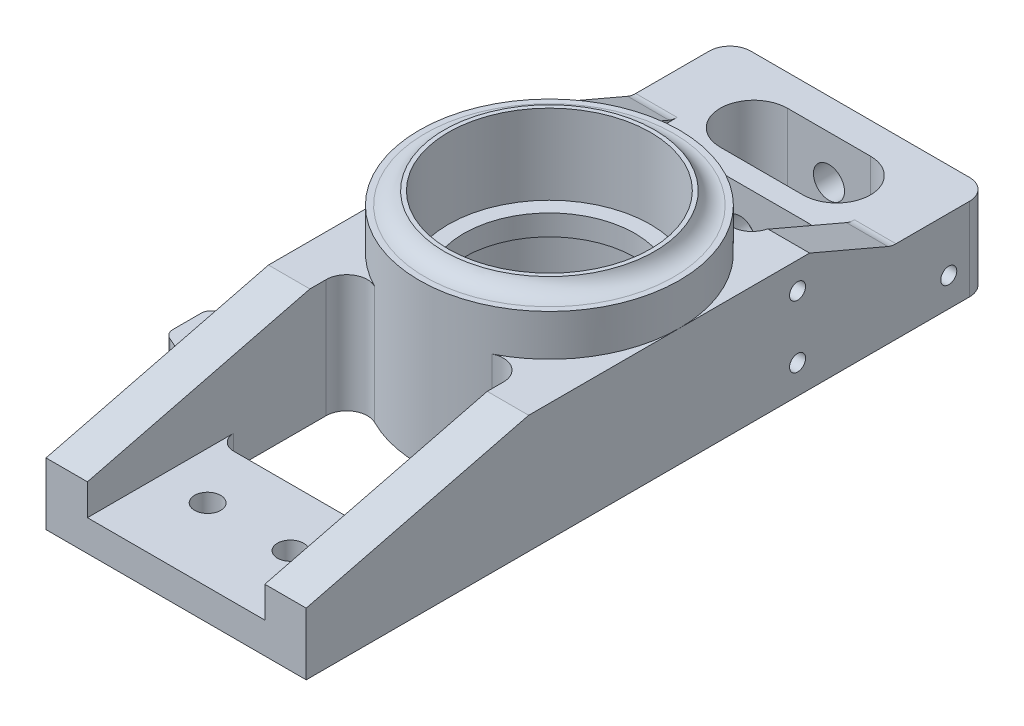
SolidWorks part; units mm, degrees
material "6061-T6 (SS)"
ref_plane "X-Y Datum" through (0, 0, 0) normal (0, 0, 1) x (1, 0, 0)
ref_plane "X-Z Datum" through (0, 0, 0) normal (0, 1, 0) x (1, 0, 0)
ref_plane "Y-Z Datum" through (0, 0, 0) normal (1, 0, 0) x (0, 0, -1)
sketch3d "KPI Sketch"
  line L0 (0, 0, 0) -> (0, 0, 50000) construction
  line L1 (0, 0, 0) -> (0, -50000, 0) construction
  line L2 (0, 0, 0) -> (-50000, 0, 0) construction
  line L3 (0, 15.9209, 92.075) -> (0, -42.747, -247.2184) construction
  line L4 (0, -13.0351, -75.3861) -> (63.9444, -13.0351, -75.3861) construction
  line L5 (63.9444, -13.0351, -75.3861) -> (63.9444, -13.0351, -23.4681) construction
  line L6 (63.9444, -13.0351, -23.4681) -> (63.9444, 11.7784, -23.4681) construction
  line L8 (0, 15.9209, 92.075) -> (0, 15.9209, -75.3861) construction
  line L9 (0, -13.0351, -75.3861) -> (0, 15.9209, -75.3861) construction
  circle A0 centre (0, 0, 0) radius 127 construction
  point P11 (0, -13.0351, -75.3861)
  point P18 (0, 0, 0)
  point P22 (0, 127, 0)
  dimension "D5" = 92.075
  dimension "D8" = 254
  dimension "D2" = 169.9461
  dimension "D3" = 28.956
  dimension "D1" = 63.9444
  dimension "D4" = 51.9179
  dimension "D6" = 24.8135
ref_axis "Wheel Spin Axis" through (0, -55.5512, 0) along (0, 1, 0)
sketch "Bearing Sketch" plane through (0, 0, 0) normal (1, 0, 0) x (0, 0, -1)
  line L11 (0, 0) -> (0, -50000) construction
  line L17 (-30.9994, -25.0922) -> (-39.8894, -25.0922)
  line L23 (-30.9994, -3.175) -> (-26.2369, -3.175)
  line L24 (55.1739, 0) -> (-55.1739, 0) construction
  line L26 (-30.9994, -3.175) -> (-30.9994, -25.0922)
  line L27 (-30.9994, 27.6332) -> (-30.9994, 3.175)
  line L28 (-30.9994, 3.175) -> (-26.2369, 3.175)
  line L29 (-26.2369, 3.175) -> (-26.2369, -3.175)
  line L31 (0, 0) -> (-50000, 0) construction
  line L33 (-30.9994, 27.6332) -> (-32.2694, 27.6332)
  line L34 (-32.2694, 27.6332) -> (-32.2694, 23.7622)
  line L35 (-32.2694, 23.7622) -> (-39.8894, 23.7622)
  line L36 (-39.8894, 23.7622) -> (-39.8894, -25.0922)
  point P3 (-26.2369, 0)
  dimension "D2" = 6.35
  dimension "D1" = 21.9172
  dimension "D4" = 24.4582
  dimension "D3" = 52.4739
  dimension "D6" = 61.9989
  dimension "D5" = 79.7789
  dimension "D7" = 64.5389
  dimension "D8" = 48.8544
revolve "Bearing Dimensions" add sketch "Bearing Sketch" angle 360 about axis through (0, -55.5512, 0) along (0, 1, 0)
sketch "UBJ Material Sketch" plane through (0, -25.0922, 0) normal (0, 1, 0) x (1, 0, 0)
  line L1 (39.8894, -46.2394) -> (-39.8894, -46.2394)
  line L3 (0, 0) -> (-50000, 0) construction
  line L4 (0, 0) -> (0, -50000) construction
  line L5 (39.8894, 0) -> (39.8894, -46.2394)
  line L7 (-39.8894, 0) -> (-39.8894, -46.2394)
  circle A0 centre (0, 0) radius 39.8894 construction
  circle A1 centre (0, 0) radius 39.8894 construction
  arc A2 (-39.8894, 0) -> (39.8894, 0) centre (0, 0) ccw
  point P5 (0, -46.2394)
  point P15 (0, -39.8894)
  dimension "D1" = 6.35
extrude "UBJ Material" add sketch "UBJ Material Sketch" along normal offset from surface (36.1544 mm away) 12.7 up to face at (0, 23.7622, -39.8894)
sketch "Sketch58" plane through (39.8894, 0, 0) normal (1, 0, 0) x (0, 0, -1)
  line L0 (0, 0) -> (-50000, 0) construction
  line L5 (0, 0) -> (0, 50000) construction
  line L14 (-46.2394, 11.0622) -> (-114.4384, -6.0422)
  line L16 (-114.4384, -6.0422) -> (-114.4384, -25.0922)
  line L17 (-114.4384, -25.0922) -> (-62.9981, -25.0922)
  line L18 (-62.9981, -25.0922) -> (-46.2394, -25.0922)
  line L19 (-46.2394, -25.0922) -> (-46.2394, 11.0622)
  line L22 (-46.2394, -25.0922) -> (0, -25.0922) construction
  point P27 (-114.4384, -15.5672)
  dimension "D1" = 19.05
  dimension "D2" = 68.199
extrude "Boss-Extrude6" add sketch "Sketch58" against normal up to surface (79.7789 mm away) contours L16 L17 L18 L19 L14 up to face at (-39.8894, -7.015, 23.1197)
sketch "Sketch9" plane through (0, -25.0922, 0) normal (0, -1, 0) x (1, 0, 0)
  line L3 (-39.8894, 0) -> (-39.8894, 114.4384) construction
  line L4 (-39.8894, 0) -> (-39.8894, 114.4384) construction
  line L5 (0, 0) -> (-50000, 0) construction
  line L7 (-27.1894, 29.1874) -> (-27.1894, 74.3672)
  line L12 (27.1894, 74.3672) -> (-27.1894, 74.3672)
  line L13 (27.1894, 74.3672) -> (27.1894, 29.1874)
  line L17 (39.8894, 114.4384) -> (39.8894, 0) construction
  line L21 (39.8894, 114.4384) -> (39.8894, 0) construction
  arc A2 (39.8894, 0) -> (-39.8894, 0) centre (0, 0) ccw construction
  arc A3 (27.1894, 29.1874) -> (-27.1894, 29.1874) centre (0, 0) ccw
  dimension "D1" = 12.7
  dimension "D2" = 12.7
extrude "UBJ Cross Member" cut sketch "Sketch9" against normal through all contours A3 L13 L12 L7 region at (0, -25.0922, 55.3249)
ref_plane "Plane1" through (0, 4.0077, 0) normal (0, -1, 0) x (-1, 0, 0)
sketch "Sketch10" plane through (0, 4.0077, -1.6553) normal (0, 1, 0) x (1, 0, 0)
  line L7 (-39.8894, -116.0937) -> (39.8894, -116.0937) construction
  line L9 (27.1894, -70.3737) -> (-27.1894, -70.3737)
  line L10 (27.1894, -70.3737) -> (27.1894, -116.0937)
  line L11 (27.1894, -116.0937) -> (-27.1894, -116.0937)
  line L12 (-27.1894, -70.3737) -> (-27.1894, -116.0937)
  line L13 (27.1894, -47.8947) -> (27.1894, -76.0225) construction
  dimension "D1" = 45.72
extrude "UBJ Mass Removal" cut sketch "Sketch10" against normal offset from surface (19.5749 mm away) 9.525 up to face at (0, -25.0922, 47.2469)
fillet "Fillet43" radius 4.7625 2 edges at (-27.1894, -20.3297, 74.3672) (27.1894, -20.3297, 74.3672)
fillet "Fillet26" radius 6.35 2 edges at (-27.1894, -7.015, 29.1874) (27.1894, -7.015, 29.1874)
fillet "Fillet45" [suppressed] radius 5.08
sketch "Sketch4" plane through (0, -25.0922, 0) normal (0, -1, 0) x (1, 0, 0)
  line L1 (-39.8894, -95.25) -> (39.8894, -95.25)
  line L3 (39.8894, 0) -> (39.8894, -95.25)
  line L4 (10.3505, 0) -> (-10.3505, 0) construction
  line L5 (0, 0) -> (0, 50000) construction
  line L7 (-39.8894, 0) -> (-39.8894, -82.55)
  line L9 (-39.8894, -95.25) -> (-39.8894, -82.55)
  arc A0 (-39.8894, 0) -> (39.8894, 0) centre (0, 0) ccw construction
  arc A1 (-39.8894, 0) -> (39.8894, 0) centre (0, 0) ccw
  point P3 (0, 0)
  dimension "D1" = 95.25
  dimension "D4" = 82.55
extrude "LBJ Material" add sketch "Sketch4" against normal offset from surface (36.1544 mm away) 12.7 up to face at (0, 23.7622, -39.8894)
sketch "Sketch7" plane through (0, -25.0922, 0) normal (0, -1, 0) x (1, 0, 0)
  line L1 (-27.1894, -58.42) -> (27.1894, -58.42)
  line L3 (0, 0) -> (50000, 0) construction
  line L4 (27.1894, -29.1874) -> (27.1894, -58.42)
  line L6 (0, 0) -> (0, 50000) construction
  line L8 (39.8894, 0) -> (39.8894, -95.25) construction
  line L9 (-27.1894, -58.42) -> (-27.1894, -29.1874)
  line L11 (-39.8894, -95.25) -> (-39.8894, 0) construction
  arc A4 (-39.8894, 0) -> (39.8894, 0) centre (0, 0) ccw construction
  arc A5 (-39.8894, 0) -> (39.8894, 0) centre (0, 0) ccw
  dimension "D1" = 12.7
  dimension "D2" = 12.7
  dimension "D3" = 58.42
extrude "Cross Members" cut sketch "Sketch7" against normal up to surface (48.8544 mm away) contours L1 region at (0, -25.0922, -47.258) up to face at (0, 23.7622, -39.8894)
sketch "Sketch62" plane through (0, 0, -95.25) normal (0, 0, -1) x (-1, 0, 0)
  line L1 (-27.1894, 0.3078) -> (27.1894, 0.3078)
  line L2 (-27.1894, 0.3078) -> (-27.1894, 11.0622)
  line L3 (-27.1894, 11.0622) -> (27.1894, 11.0622)
  line L4 (27.1894, 0.3078) -> (27.1894, 11.0622)
  line L5 (-39.8894, 11.0622) -> (-39.8894, -25.0922) construction
  dimension "D1" = 12.7
extrude "Cut-Extrude1" cut sketch "Sketch62" against normal blind 44.45
sketch "Sketch5" plane through (0, -25.0922, 0) normal (0, -1, 0) x (1, 0, 0)
  line L0 (0, 0) -> (50000, 0) construction
  line L1 (0, 0) -> (0, 50000) construction
  line L2 (12.7, -75.3861) -> (-12.7, -75.3861) construction
  line L3 (12.7, -85.7112) -> (-12.7, -85.7112)
  line L4 (12.7, -65.061) -> (-12.7, -65.061)
  arc A0 (12.7, -85.7112) -> (12.7, -65.061) centre (12.7, -75.3861) ccw
  arc A1 (-12.7, -65.061) -> (-12.7, -85.7112) centre (-12.7, -75.3861) ccw
  point P8 (0, -75.3861)
  dimension "D2" = 10.3251
  dimension "D1" = 12.7
extrude "LBJ Opening" cut sketch "Sketch5" against normal up to surface (25.4 mm away) up to face at (0, 0.3078, -76.835)
fillet "LBJ Outside" radius 6.35 2 edges at (39.8894, -7.015, -95.25) (-39.8894, -7.015, -95.25)
fillet "LBJ Ramp" radius 6.35 4 edges at (-27.1894, -12.3922, -58.42) (27.1894, -12.3922, -58.42) (-27.1894, -7.015, -29.1874) (27.1894, -7.015, -29.1874)
fillet "BH Lip" radius 6.35 1 edges at (0, 23.7622, -32.2694)
hole_wizard "Ø8.0mm Dowel Hole1" positions "Sketch25" profile "Sketch26" hole size "Ø8.0" standard "ANSI Metric"
sketch "Sketch25" plane through (0, -15.5672, 0) normal (0, 1, 0) x (1, 0, 0)
  line L0 (12.7, -92.075) -> (-12.7, -92.075) construction
  line L2 (0, 200000) -> (0, -250000) construction
  line L5 (0, 0) -> (0, -50000) construction
  line L6 (0, 0) -> (-50000, 0) construction
  point P0 (12.7, -92.075)
  point P2 (-12.7, -92.075)
  dimension "D1" = 12.7
  dimension "D2" = 12.7
  dimension "D3" = 92.075
sketch "Sketch26" plane through (12.7, -15.5672, 92.075) normal (1, 0, 0) x (0, 0, 1)
  line L0 (0, 0) -> (0, 16.002)
  line L1 (0, 16.002) -> (4, 13.5986)
  line L2 (4, 13.5986) -> (4, 0)
  line L5 (4, 0) -> (0, 0)
  line L10 (0, 16.002) -> (-4, 13.5986) construction
  line L11 (0, -6.35) -> (0, 107.95) construction
  dimension "Hole Dia." = 8
  dimension "Hole Depth" = 16.002
  dimension "Drill Angle" = 118
sketch "Sketch30" plane through (0, -25.0922, 0) normal (0, -1, 0) x (1, 0, 0)
  line L1 (0, 0) -> (-50000, 0) construction
  line L2 (0, 0) -> (0, 50000) construction
  line L6 (-39.8894, -31.4891) -> (-39.8894, -65.3856)
  line L18 (-63.4528, -56.9861) -> (-53.5589, -60.5129)
  line L19 (-63.4528, -43.0161) -> (-39.8894, -31.4891)
  line L20 (-63.4197, 41.3533) -> (-39.8894, 30.3086)
  line L21 (-63.4197, 54.04) -> (-39.8894, 64.2936)
  line L22 (-39.8894, 64.2936) -> (-39.8894, 30.3086)
  line L23 (-53.5589, -60.5129) -> (-39.8894, -65.3856)
  line L24 (-63.4528, -43.0161) -> (-63.4528, -56.9861)
  line L25 (-63.4197, 54.04) -> (-63.4197, 41.3533)
  line L27 (-39.8894, -88.9) -> (-39.8894, 0) construction
  line L28 (-39.8894, 46.2394) -> (-39.8894, 0) construction
  line L29 (-39.8894, -88.9) -> (-39.8894, 114.4384) construction
  circle A2 centre (-55.6468, -48.8308) radius 3 construction
  circle A3 centre (-55.6468, 47.1692) radius 3 construction
  point P50 (-55.6468, -48.8308)
  point P51 (-55.6468, 47.1692)
  dimension "D1" = 96
  dimension "D2" = 55.6468
  dimension "D3" = 6
extrude "Boss-Extrude1" add sketch "Sketch30" against normal blind 10.16
fillet "Fillet33" radius 3.175 4 edges at (-63.4197, -20.0122, 41.3533) (-63.4197, -20.0122, 54.04) (-63.4528, -20.0122, -43.0161) (-63.4528, -20.0122, -56.9861)
fillet "Fillet34" radius 6.35 4 edges at (-39.8894, -20.0122, -65.3856) (-39.8894, -20.0122, -31.4891) (-39.8894, -20.0122, 30.3086) (-39.8894, -20.0122, 64.2936)
hole_wizard "CBORE for M8 Hex Head Bolt1" positions "Sketch32" profile "Sketch33" counterbore size "M8" standard "ANSI Metric"
sketch "Sketch32" plane through (0, -25.0922, 0) normal (0, 1, 0) x (1, 0, 0)
  point P9 (-55.6468, -47.1692)
  point P12 (-55.6468, 48.8308)
sketch "Sketch33" plane through (-55.6468, -25.0922, 47.1692) normal (1, 0, 0) x (0, 0, -1)
  line L0 (0, 0) -> (0, 16.002)
  line L1 (0, 16.002) -> (4.2, 13.4784)
  line L2 (4.2, 13.4784) -> (4.2, 5)
  line L3 (4.2, 5) -> (6.75, 5)
  line L4 (6.75, 5) -> (6.75, 0)
  line L5 (6.75, 0) -> (0, 0)
  line L10 (0, 16.002) -> (-4.2, 13.4784) construction
  line L11 (0, -6.35) -> (0, 107.95) construction
  dimension "Hole Dia." = 8.4
  dimension "Hole Depth" = 16.002
  dimension "C'Bore Dia." = 13.5
  dimension "C'Bore Depth" = 5
  dimension "Drill Angle" = 118
chamfer "Chamfer1" [suppressed] distance 1.5875 angle 45
sketch "Sketch34" plane through (0, -25.0922, 0) normal (0, -1, 0) x (1, 0, 0)
  circle A0 centre (0, 0) radius 50.4825 construction
  circle A1 centre (50.4825, 0) radius 5.9531 construction
  point P3 (50.4825, 0)
  dimension "D1" = 100.965
  dimension "D3" = 11.9062
sketch "Sketch37" plane through (0, -25.0922, 0) normal (0, -1, 0) x (1, 0, 0)
  line L1 (-39.8894, -88.9) -> (-39.8894, 0) construction
  line L5 (-39.8894, -11.1125) -> (-58.9394, -11.1125)
  line L10 (-39.8894, -11.1125) -> (-39.8894, 11.1125)
  line L12 (-39.8894, 11.1125) -> (-58.9394, 11.1125)
  line L13 (-58.9394, -11.1125) -> (-58.9394, 11.1125)
  line L15 (200000, 0) -> (-250000, 0) construction
  point P7 (-58.9394, 0)
  dimension "D2" = 19.05
  dimension "D3" = 22.225
extrude "Speed Sensor Extrude" add sketch "Sketch37" against normal blind 7.716
hole_wizard "3/8 (0.375) Diameter Hole2" positions "Sketch50" profile "Sketch51" hole size "3/8" standard "ANSI Inch"
sketch "Sketch50" plane through (0, 0, -95.25) normal (0, 0, -1) x (-1, 0, 0)
  point P0 (0, -13.0351)
sketch "Sketch51" plane through (0, -13.0351, -95.25) normal (1, 0, 0) x (0, 1, 0)
  line L0 (0, 0) -> (0, 39.6916)
  line L1 (0, 39.6916) -> (4.7625, 36.83)
  line L2 (4.7625, 36.83) -> (4.7625, 0)
  line L5 (4.7625, 0) -> (0, 0)
  line L10 (0, 39.6916) -> (-4.7625, 36.83) construction
  line L11 (0, -6.35) -> (0, 107.95) construction
  dimension "Hole Dia." = 9.525
  dimension "Hole Depth" = 36.83
  dimension "Drill Angle" = 118
fillet "Fillet47" radius 6.35 4 edges at (-39.8894, -21.2341, 11.1125) (-58.9394, -21.2341, 11.1125) (-39.8894, -21.2341, -11.1125) (-58.9394, -21.2341, -11.1125)
hole_wizard "15/32 (0.46875) Diameter Hole1" positions "Sketch35" profile "Sketch36" hole size "15/32" standard "ANSI Inch"
sketch "Sketch35" plane through (0, -17.3761, 0) normal (0, 1, 0) x (1, 0, 0)
  line L0 (200000, 0) -> (-250000, 0) construction
  circle A0 centre (0, 0) radius 50.4825 construction
  point P0 (-50.4825, 0)
sketch "Sketch36" plane through (-50.4825, -17.3761, 0) normal (1, 0, 0) x (0, 0, 1)
  line L0 (0, 0) -> (0, 16.002)
  line L1 (0, 16.002) -> (5.9531, 12.425)
  line L2 (5.9531, 12.425) -> (5.9531, 0)
  line L5 (5.9531, 0) -> (0, 0)
  line L10 (0, 16.002) -> (-5.9531, 12.425) construction
  line L11 (0, -6.35) -> (0, 107.95) construction
  dimension "Hole Dia." = 11.9062
  dimension "Hole Depth" = 16.002
  dimension "Drill Angle" = 118
fillet "Fillet49" [suppressed] radius 4.7625
sketch "Sketch59" plane through (39.8894, 0, 0) normal (-1, 0, 0) x (0, 0, 1)
  line L0 (114.4384, -25.0922) -> (-88.9, -25.0922) construction
  line L1 (-95.25, 11.0622) -> (-95.25, -25.0922) construction
  point P0 (-36.195, 2.8478)
  point P1 (-36.195, -16.2022)
  point P4 (-82.55, -16.2022)
  dimension "D1" = 19.05
  dimension "D2" = 46.355
  dimension "D3" = 8.89
  dimension "D4" = 12.7
hole_wizard "#10 (0.1935) Diameter Hole1" positions "Sketch60" profile "Sketch61" hole size "#10" standard "ANSI Inch"
sketch "Sketch60" plane through (39.8894, 0, 0) normal (-1, 0, 0) x (0, 0, 1)
  point P0 (-82.55, -16.2022)
  point P6 (-36.195, 2.8478)
  point P9 (-36.195, -16.2022)
sketch "Sketch61" plane through (39.8894, -16.2022, -82.55) normal (0, 1, 0) x (0, 0, -1)
  line L0 (0, 0) -> (0, 11.1125)
  line L1 (0, 11.1125) -> (2.4574, 9.6359)
  line L2 (2.4574, 9.6359) -> (2.4574, 0)
  line L5 (2.4574, 0) -> (0, 0)
  line L10 (0, 11.1125) -> (-2.4575, 9.6359) construction
  line L11 (0, -6.35) -> (0, 107.95) construction
  dimension "Hole Dia." = 4.9149
  dimension "Hole Depth" = 11.1125
  dimension "Drill Angle" = 118
sketch "Sketch63" plane through (-39.8894, 0, 0) normal (-1, 0, 0) x (0, 0, 1)
  line L1 (-88.9, 11.0622) -> (0, 11.0622) construction
  line L2 (-39.8894, 23.7622) -> (-39.8894, -25.0922) construction
  line L5 (-95.25, 0.3078) -> (-65.061, 0.3078)
  line L6 (-65.061, 0.3078) -> (-39.8894, 11.0622)
  line L7 (-39.8894, 11.0622) -> (-95.25, 11.0622)
  line L8 (-95.25, 11.0622) -> (-95.25, 0.3078)
extrude "Cut-Extrude2" cut sketch "Sketch63" against normal through all
fillet "Fillet50" radius 6.35 2 edges at (33.5394, 0.3078, -65.061) (-33.5394, 0.3078, -65.061)
equation "\"KPI\"= 9.56"
equation "\"TOE alng x\"= 77.1mm"
equation "\"x dtm to toe\"= 36.4mm"
equation "\"XY to toe\"= 30.7mm"
equation "\"XZ to LBJ\"= 22.08mm"
equation "\"XY to LBJ\"= 3.2"
equation "\"XY to UBJ\"=3.625"
equation "\"Bearing Inner Bore\"= 1.25'RADIUS"
equation "\"Bearing Outer Bore\"= 2.4409'RADIUS"
equation "\"Bearing Thickness\"= .7150"
equation "\"D1@Bearing Sketch\"=\"Bearing Thickness\" +.25-0.09712-0.005"
equation "\"D4@Bearing Sketch\"=\"Bearing Thickness\" +.2625-0.06458+.05"
equation "\"D3@Bearing Sketch\"=\"Bearing Outer Bore\" - .375"
equation "\"D6@Bearing Sketch\" = \"Bearing Outer Bore\""
equation "\"D5@Bearing Sketch\" = \"Bearing Outer Bore\" + 2 * .35"
equation "\"D7@Bearing Sketch\" = \"Bearing Outer Bore\" + .1"
equation "\"D8@Bearing Sketch\"=\"Bearing Thickness\" * 2 + 0.225 + 0.2684"
equation "\"D1@Sketch4\"=\"XY to LBJ\" + .25+.3"
equation "\"D1Sketch21\"= \"XY to UBJ\" + 0.375"
equation "\"D3@Sketch25\"=\"XY to UBJ\""
equation "\"D5@KPI Sketch\"=\"XY to UBJ\""
